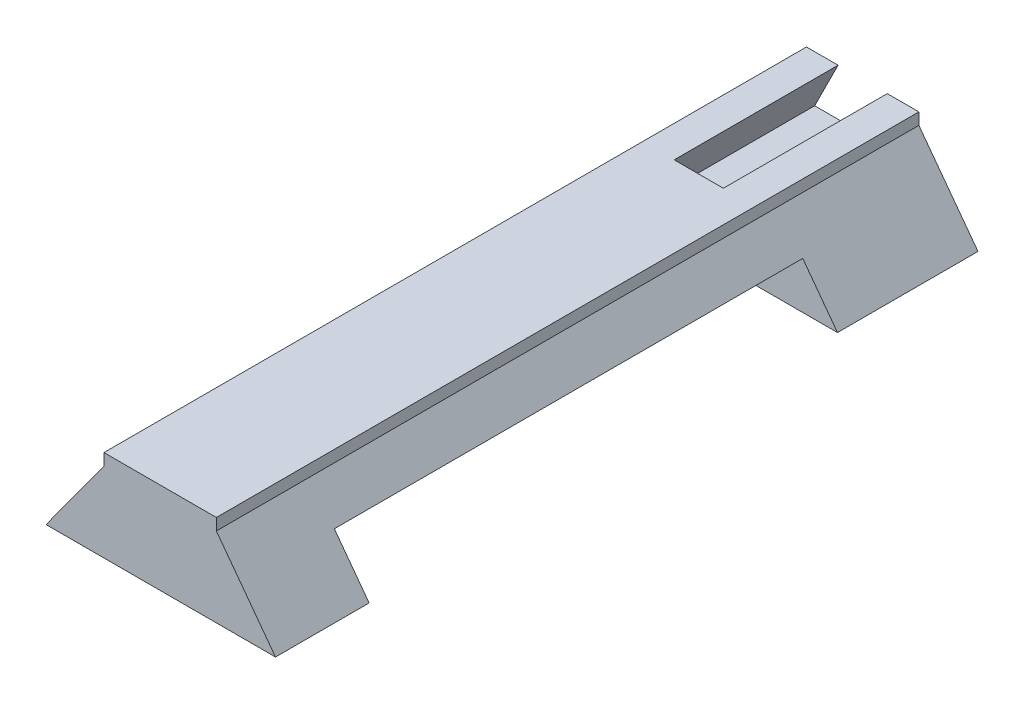
SolidWorks part; units mm, degrees
ref_plane "Front Plane" through (0, 0, 0) normal (0, 0, 1) x (1, 0, 0)
ref_plane "Top Plane" through (0, 0, 0) normal (0, 1, 0) x (1, 0, 0)
ref_plane "Right Plane" through (0, 0, 0) normal (1, 0, 0) x (0, 0, -1)
sketch "Sketch1" plane through (0, 0, 0) normal (0, 0, 1) x (1, 0, 0)
  line L2 (-4.95, -3.4) -> (4.85, -3.4)
  line L3 (-2.475, 0) -> (-4.95, -3.4)
  line L4 (2.325, 0) -> (4.85, -3.4)
  line L7 (-2.475, 0) -> (-2.475, 0.5)
  line L8 (-2.475, 0.5) -> (2.325, 0.5)
  line L9 (2.325, 0) -> (2.325, 0.5)
  point P4 (0, 0)
  point P10 (-0.05, -3.4)
  dimension "D1" = 3.4
  dimension "D2" = 4.8
  dimension "D3" = 9.8
  dimension "D4" = 0.5
  dimension "D6" = 0.5
extrude "Boss-Extrude1" add sketch "Sketch1" along normal blind 30
sketch "Sketch3" plane through (0, 0, 0) normal (1, 0, 0) x (0, 0, -1)
  line L0 (-30, -3.4) -> (-30, 0) construction
  line L1 (-26, -3.4) -> (-6, -3.4)
  line L2 (-26, -3.4) -> (-26, -1.4)
  line L3 (-26, -1.4) -> (-6, -1.4)
  line L4 (-6, -3.4) -> (-6, -1.4)
  line L5 (-30, -3.4) -> (0, -3.4) construction
  dimension "D1" = 4
  dimension "D2" = 20
  dimension "D3" = 2
  dimension "D4" = 0
extrude "Cut-Extrude1" cut sketch "Sketch3" against normal through all both and the other way through all
sketch "Sketch4" plane through (0, 0, 0) normal (0, 0, -1) x (-1, 0, 0)
  line L0 (0.075, 0.5) -> (0.075, -3.4) construction
  line L3 (-2.325, 0.5) -> (2.475, 0.5) construction
  line L4 (4.95, -3.4) -> (-4.85, -3.4) construction
  line L5 (-1.975, -1.5) -> (2.125, -1.5)
  line L6 (-1.975, -1.5) -> (-0.975, 0.5)
  line L7 (-0.975, 0.5) -> (1.125, 0.5)
  line L8 (1.125, 0.5) -> (2.125, -1.5)
  point P9 (0.075, -1.5)
  dimension "D1" = 4.1
  dimension "D2" = 2.1
  dimension "D3" = 1.05
  dimension "D4" = 2
extrude "Cut-Extrude2" cut sketch "Sketch4" against normal blind 7
